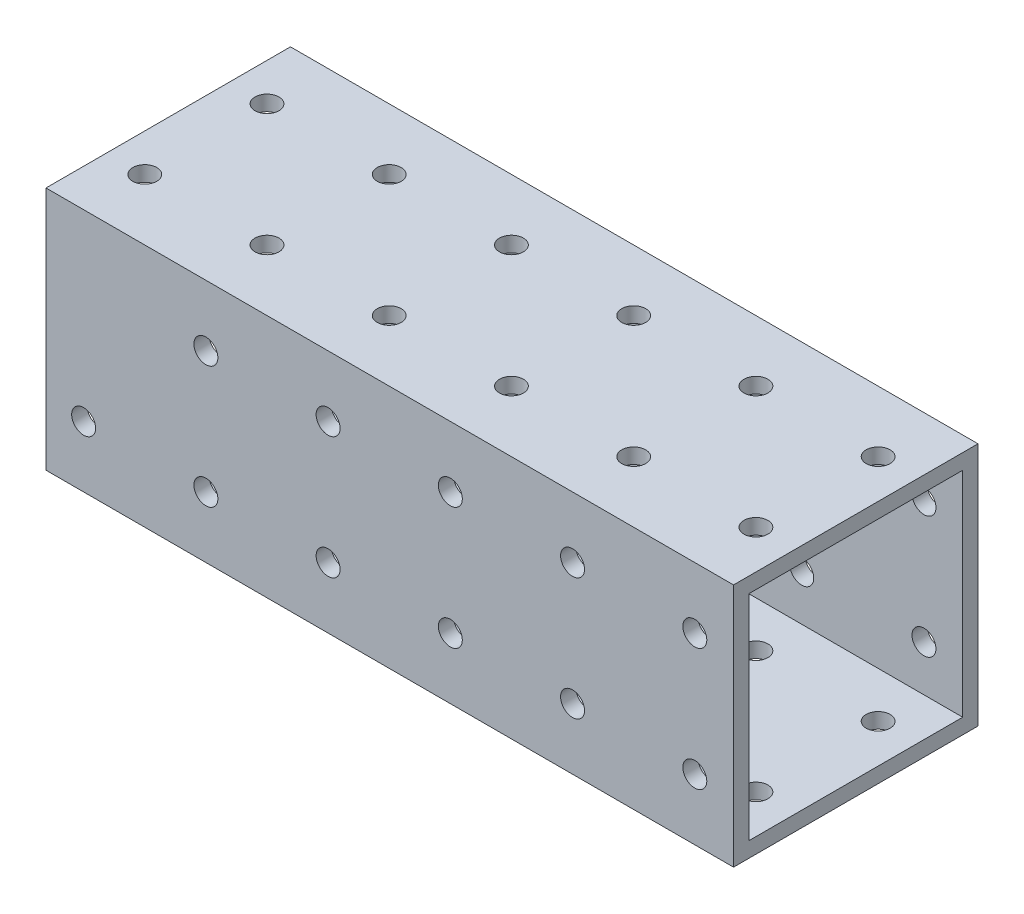
SolidWorks part; units mm, degrees
material "6061-T6 (SS)"
ref_plane "Front Plane" through (0, 0, 0) normal (0, 0, 1) x (1, 0, 0)
ref_plane "Top Plane" through (0, 0, 0) normal (0, 1, 0) x (1, 0, 0)
ref_plane "Right Plane" through (0, 0, 0) normal (1, 0, 0) x (0, 0, -1)
sketch "Sketch1" plane through (0, 0, 0) normal (1, 0, 0) x (0, 0, -1)
  line L1 (0, 0) -> (50.8, 0)
  line L2 (0, 0) -> (0, 50.8)
  line L3 (0, 50.8) -> (50.8, 50.8)
  line L4 (50.8, 0) -> (50.8, 50.8)
  dimension "D1" = 50.8
extrude "Boss-Extrude1" add sketch "Sketch1" along normal blind 142.875
shell "Shell1" thickness 3.175 removed face at (0, 25.4, -25.4) removed face at (142.875, 25.4, -25.4)
sketch "Sketch2" plane through (0, 0, -50.8) normal (0, 0, -1) x (-1, 0, 0)
  line L1 (-142.875, 0) -> (0, 0) construction
  line L3 (-142.875, 0) -> (-142.875, 50.8) construction
  circle A22 centre (-7.8232, 38.1) radius 2.4892 construction
  circle A23 centre (-33.2232, 38.1) radius 2.4892
  circle A24 centre (-58.6232, 38.1) radius 2.4892
  circle A25 centre (-84.0232, 38.1) radius 2.4892
  circle A26 centre (-109.4232, 38.1) radius 2.4892
  circle A27 centre (-134.8232, 38.1) radius 2.4892
  circle A28 centre (-33.2232, 12.7) radius 2.4892
  circle A29 centre (-58.6232, 12.7) radius 2.4892
  circle A30 centre (-84.0232, 12.7) radius 2.4892
  circle A31 centre (-109.4232, 12.7) radius 2.4892
  circle A32 centre (-134.8232, 12.7) radius 2.4892
  circle A33 centre (-7.8232, 12.7) radius 2.4892
  dimension "D5" = 2
  dimension "D3" = 38.1
  dimension "D1" = 4.9784
  dimension "D2" = 135.0518
  dimension "D4" = 6
  dimension "D6" = 25.4
  dimension "D7" = 25.4
extrude "Cut-Extrude1" cut sketch "Sketch2" against normal through all contours A31 | A32 | A28 | A26 | A25 | A30 | A24 | A29 | A23 | A22 | A33 | A27 region at (33.2232, 38.1, -50.8) region at (58.6232, 38.1, -50.8) region at (84.0232, 38.1, -50.8) region at (109.4232, 38.1, -50.8) region at (134.8232, 38.1, -50.8) region at (33.2232, 12.7, -50.8) region at (58.6232, 12.7, -50.8) region at (84.0232, 12.7, -50.8) region at (109.4232, 12.7, -50.8) region at (134.8232, 12.7, -50.8) region at (7.8232, 12.7, -50.8)
sketch "Sketch3" plane through (0, 0, 0) normal (0, -1, 0) x (1, 0, 0)
  line L0 (142.875, 0) -> (142.875, -50.8) construction
  line L1 (142.875, -50.8) -> (0, -50.8) construction
  circle A2 centre (134.8232, -12.7) radius 2.4892
  circle A3 centre (109.4232, -12.7) radius 2.4892
  circle A4 centre (84.0232, -12.7) radius 2.4892
  circle A5 centre (58.6232, -12.7) radius 2.4892
  circle A6 centre (33.2232, -12.7) radius 2.4892
  circle A7 centre (7.8232, -12.7) radius 2.4892
  circle A8 centre (109.4232, -38.1) radius 2.4892
  circle A9 centre (84.0232, -38.1) radius 2.4892
  circle A10 centre (58.6232, -38.1) radius 2.4892
  circle A11 centre (33.2232, -38.1) radius 2.4892
  circle A12 centre (7.8232, -38.1) radius 2.4892
  circle A13 centre (134.8232, -38.1) radius 2.4892
  dimension "D1" = 4.9784
  dimension "D2" = 8.0518
  dimension "D3" = 38.1
  dimension "D6" = 25.4
  dimension "D7" = 25.4
  dimension "D4" = 6
  dimension "D5" = 2
extrude "Cut-Extrude2" cut sketch "Sketch3" against normal through all
